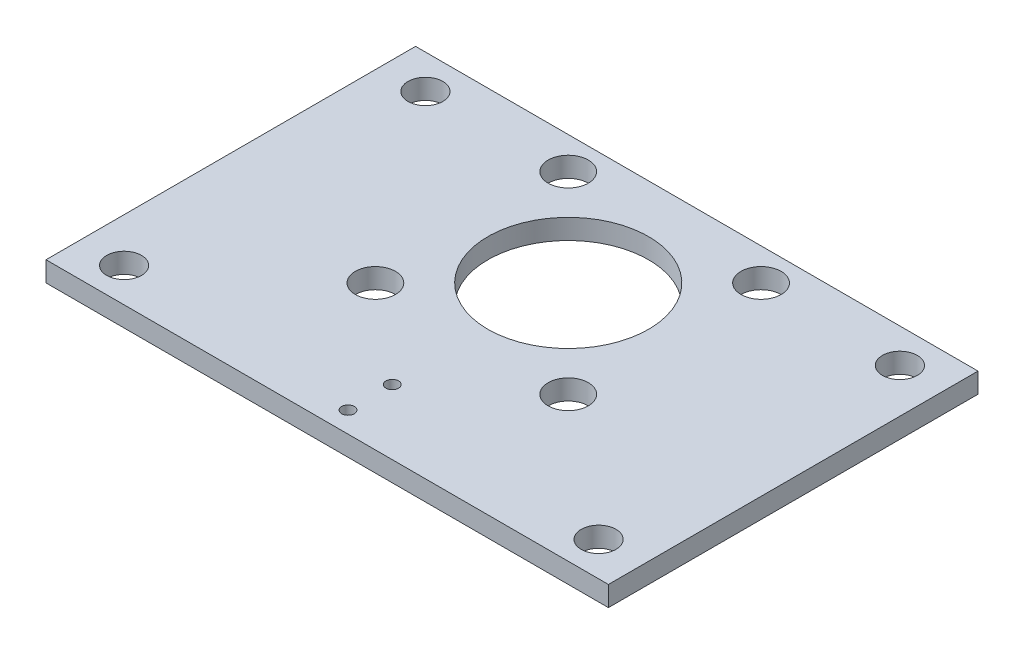
SolidWorks part; units mm, degrees
ref_plane "Front Plane" through (0, 0, 0) normal (0, 0, 1) x (1, 0, 0)
ref_plane "Top Plane" through (0, 0, 0) normal (0, 1, 0) x (1, 0, 0)
ref_plane "Right Plane" through (0, 0, 0) normal (1, 0, 0) x (0, 0, -1)
sketch "Sketch1" plane through (0, 0, 0) normal (0, 1, 0) x (1, 0, 0)
  line L1 (-88.9, 40.64) -> (88.9, 40.64)
  line L2 (-88.9, 40.64) -> (-88.9, -76.2)
  line L4 (88.9, 40.64) -> (88.9, -76.2)
  line L9 (-88.9, -76.2) -> (88.9, -76.2)
  point P0 (0, 0)
  point P10 (0, -76.2)
  dimension "D1" = 116.84
  dimension "D2" = 177.8
  dimension "D4" = 76.2
extrude "Boss-Extrude1" add sketch "Sketch1" along normal mid plane 6.35
hole_wizard "1 (1) Diameter Hole1" positions "Sketch3" profile "Sketch2" hole size "1" standard "ANSI Inch" end condition through all
sketch "Sketch3" plane through (0, 3.175, 0) normal (0, 1, 0) x (1, 0, 0)
  point P0 (0, 0)
sketch "Sketch2" plane through (0, 3.175, 0) normal (1, 0, 0) x (0, 0, 1)
  line L0 (0, 0) -> (0, 6.35)
  line L1 (0, 6.35) -> (25.4, 6.35)
  line L2 (25.4, 6.35) -> (25.4, 0)
  line L5 (25.4, 0) -> (0, 0)
  line L11 (0, -6.35) -> (0, 107.95) construction
  dimension "Thru Hole Dia." = 50.8
  dimension "Thru Hole Depth" = 6.35
hole_wizard "1/2 (0.5) Diameter Hole1" positions "Sketch5" profile "Sketch4" hole size "1/2" standard "ANSI Inch" end condition through all
sketch "Sketch5" plane through (0, 3.175, 0) normal (0, 1, 0) x (1, 0, 0)
  line L1 (-30.48, 30.48) -> (30.48, 30.48)
  line L2 (-30.48, 30.48) -> (-30.48, -30.48)
  line L3 (-30.48, -30.48) -> (30.48, -30.48)
  line L4 (30.48, 30.48) -> (30.48, -30.48)
  line L5 (-30.48, 30.48) -> (30.48, -30.48) construction
  line L6 (-30.48, -30.48) -> (30.48, 30.48) construction
  point P2 (30.48, -30.48)
  point P5 (-30.48, 30.48)
  point P6 (-30.48, -30.48)
  point P7 (30.48, 30.48)
  dimension "D1" = 60.96
sketch "Sketch4" plane through (30.48, 3.175, 30.48) normal (1, 0, 0) x (0, 0, 1)
  line L0 (0, 0) -> (0, 6.35)
  line L1 (0, 6.35) -> (6.35, 6.35)
  line L2 (6.35, 6.35) -> (6.35, 0)
  line L5 (6.35, 0) -> (0, 0)
  line L11 (0, -6.35) -> (0, 107.95) construction
  dimension "Thru Hole Dia." = 12.7
  dimension "Thru Hole Depth" = 6.35
hole_wizard "Ø4.0 (4) Diameter Hole1" positions "Sketch7" profile "Sketch6" hole size "Ø4.0" standard "ANSI Metric" end condition through all
sketch "Sketch7" plane through (0, 3.175, 0) normal (0, 1, 0) x (1, 0, 0)
  point P0 (0, -55.63)
  point P2 (0, -69.63)
  dimension "D1" = 55.63
  dimension "D2" = 14
sketch "Sketch6" plane through (0, 3.175, 55.63) normal (1, 0, 0) x (0, 0, 1)
  line L0 (0, 0) -> (0, 6.35)
  line L1 (0, 6.35) -> (2, 6.35)
  line L2 (2, 6.35) -> (2, 0)
  line L5 (2, 0) -> (0, 0)
  line L11 (0, -6.35) -> (0, 107.95) construction
  dimension "Thru Hole Dia." = 4
  dimension "Thru Hole Depth" = 6.35
hole_wizard "M10 Clearance Hole1" positions "Sketch9" profile "Sketch8" hole size "M10" standard "ANSI Metric" end condition through all
sketch "Sketch9" plane through (0, 3.175, 0) normal (0, 1, 0) x (1, 0, 0)
  line L1 (-75, 29.845) -> (75, 29.845)
  line L2 (-75, 29.845) -> (-75, -65.405)
  line L3 (-75, -65.405) -> (75, -65.405)
  line L4 (75, 29.845) -> (75, -65.405)
  line L5 (88.9, -17.78) -> (-88.9, -17.78) construction
  line L6 (88.9, -76.2) -> (88.9, 40.64) construction
  line L7 (-88.9, 40.64) -> (-88.9, -76.2) construction
  point P2 (75, -65.405)
  point P5 (-75, 29.845)
  point P6 (-75, -65.405)
  point P7 (75, 29.845)
  point P17 (75, -17.78)
  point P18 (0, 29.845)
  dimension "D1" = 95.25
  dimension "D2" = 150
sketch "Sketch8" plane through (75, 3.175, 65.405) normal (1, 0, 0) x (0, 0, 1)
  line L0 (0, 0) -> (0, 6.35)
  line L1 (0, 6.35) -> (5.5, 6.35)
  line L2 (5.5, 6.35) -> (5.5, 0)
  line L5 (5.5, 0) -> (0, 0)
  line L11 (0, -6.35) -> (0, 107.95) construction
  dimension "Thru Hole Dia." = 11
  dimension "Thru Hole Depth" = 6.35
